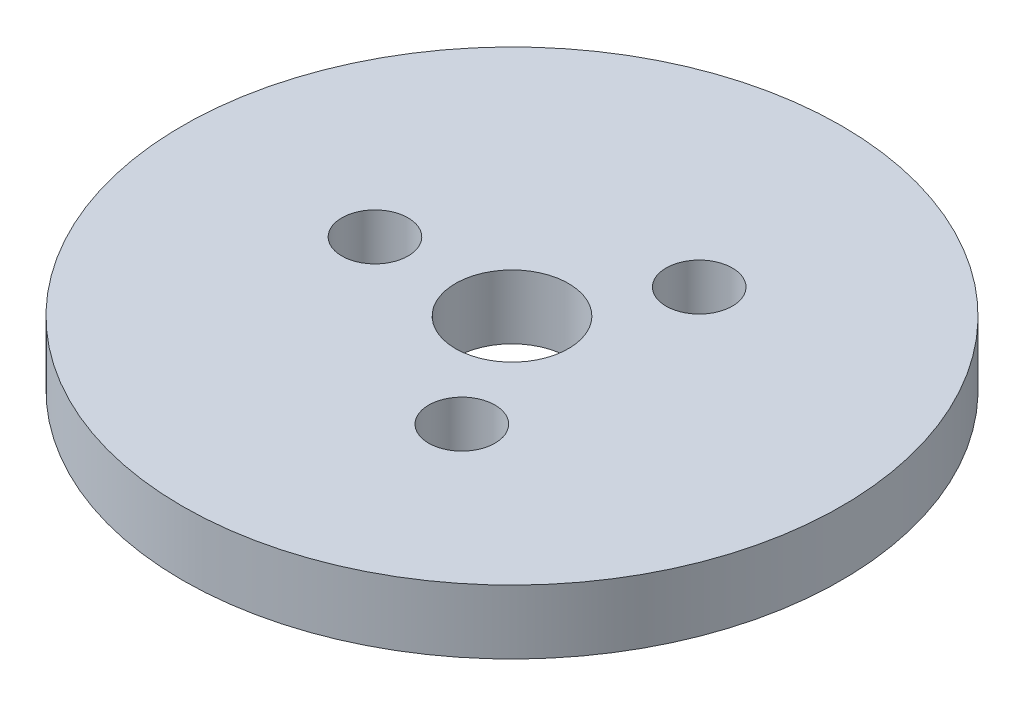
SolidWorks part; units mm, degrees
ref_plane "Front Plane" through (0, 0, 0) normal (0, 0, 1) x (1, 0, 0)
ref_plane "Top Plane" through (0, 0, 0) normal (0, 1, 0) x (1, 0, 0)
ref_plane "Right Plane" through (0, 0, 0) normal (1, 0, 0) x (0, 0, -1)
sketch "Sketch1" plane through (0, 0, 0) normal (0, 1, 0) x (1, 0, 0)
  circle A0 centre (0, 0) radius 87.5
  dimension "FLANGE_OD" = 175
extrude "Boss-Extrude1" add sketch "Sketch1" along normal blind 17
sketch "Sketch2" plane through (0, 0, 0) normal (0, 1, 0) x (1, 0, 0)
  circle A0 centre (0, 0) radius 15
  dimension "BORE_D" = 30
extrude "Cut-Extrude1" cut sketch "Sketch2" along normal through all
sketch "Sketch3" plane through (0, 17, 0) normal (0, 1, 0) x (1, 0, 0)
  circle A0 centre (0, 0) radius 36.3876 construction
  circle A1 centre (-36.3876, 0) radius 8.7915
  dimension "BOLT_D" = 17.583
  dimension "BOLT_PCD" = 72.7752
extrude "Cut-Extrude2" cut sketch "Sketch3" against normal blind 14.7635
pattern_circular "CirPattern1" count 3 over 360 about axis through (0, 0, 0) along (0, 1, 0) of "Cut-Extrude2"
